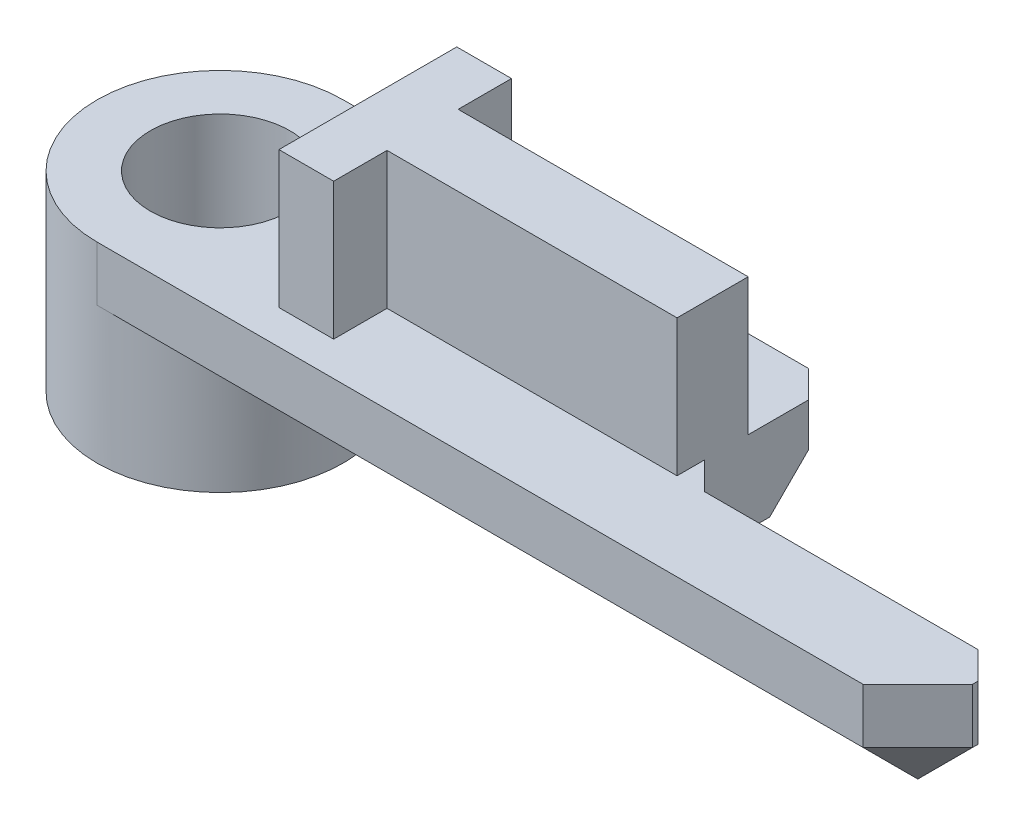
SolidWorks part; units mm, degrees
note: The reader was unsure of these and kept them because the rebuilt part matched: shared geometry of "Sketch3<4>".
ref_plane "Front Plane" through (0, 0, 0) normal (0, 0, 1) x (1, 0, 0)
ref_plane "Top Plane" through (0, 0, 0) normal (0, 1, 0) x (1, 0, 0)
ref_plane "Right Plane" through (0, 0, 0) normal (1, 0, 0) x (0, 0, -1)
sketch "Sketch1" plane through (0, 0, 0) normal (0, 1, 0) x (1, 0, 0)
  circle A0 centre (0, 0) radius 2.55
  circle A1 centre (0, 0) radius 4.5
  dimension "D1" = 5.1
  dimension "D2" = 9
extrude "Boss-Extrude1" add sketch "Sketch1" along normal blind 3
sketch "Sketch2" plane through (0, 3, 0) normal (0, 1, 0) x (1, 0, 0)
  line L1 (0, -4.5) -> (30, -4.5)
  line L3 (0, 4.5) -> (30, 4.5)
  line L4 (30, -4.5) -> (30, 4.5)
  circle A0 centre (0, 0) radius 2.55 construction
  circle A1 centre (0, 0) radius 4.5
  arc A2 (0, 4.5) -> (0, -4.5) centre (0, 0) ccw
  circle A3 centre (0, 0) radius 2.55
  dimension "D2" = 30
  dimension "D1" = 0
extrude "Boss-Extrude2" add sketch "Sketch2" along normal blind 4
chamfer "Chamfer1" distance 2 angle 45 5 edges at (15, 3, 4.5) (30, 5, 4.5) (30, 3, 0) (15, 3, -4.5) (30, 5, -4.5)
sketch "Sketch3" plane through (0, 7, 0) normal (0, 1, 0) x (1, 0, 0)
  line L0 (-4.5, 0) -> (6.4, 0) construction
  line L2 (5.4, -3.25) -> (7.4, -3.25)
  line L3 (5.4, -3.25) -> (5.4, 3.25)
  line L4 (5.4, 3.25) -> (7.4, 3.25)
  line L5 (0, -4.5) -> (28, -4.5)
  line L6 (28, -4.5) -> (30, -2.5)
  line L7 (30, -2.5) -> (30, 2.5)
  line L8 (30, 2.5) -> (28, 4.5)
  line L9 (28, 4.5) -> (0, 4.5)
  line L10 (0, -4.5) -> (28, -4.5)
  line L11 (28, -4.5) -> (30, -2.5)
  line L12 (30, -2.5) -> (30, 2.5)
  line L13 (30, 2.5) -> (28, 4.5)
  line L14 (28, 4.5) -> (0, 4.5)
  line L15 (7.4, -3.25) -> (7.4, -1.3)
  line L16 (5.4, -3.25) -> (7.4, 3.25) construction
  line L17 (5.4, 3.25) -> (7.4, -3.25) construction
  line L22 (18, -1.3) -> (18, 4.5)
  line L23 (7.4, -1.3) -> (18, -1.3)
  line L25 (7.4, 1.3) -> (7.4, 3.25)
  line L28 (30, -1.3) -> (18, -1.3)
  line L29 (7.4, 1.3) -> (18, 1.3)
  line L30 (18, 0) -> (30, 0) construction
  arc A1 (0, 4.5) -> (0, -4.5) centre (0, 0) ccw
  arc A2 (0, 4.5) -> (0, -4.5) centre (0, 0) ccw
  point P8 (6.4, 0)
  line M23 (30, 2.5) -> (28, 4.5)
  line M24 (28, 4.5) -> (0, 4.5)
  dimension "D2" = 2
  dimension "D3" = 12
  dimension "D4" = 5.8
  dimension "D5" = 6.5
  dimension "D7" = 6.4
  dimension "D1" = 0
extrude "Cut-Extrude1" cut sketch "Sketch3" against normal through all contours L28 L12 L22 M23 M24
extrude "Boss-Extrude4" add sketch "Sketch3<4>" along normal blind 5 contours L29 L25 L4 L3 L2 L15 L23 L22
sketch "Sketch3<4>" plane through (0, 7, 0) normal (0, 1, 0) x (1, 0, 0) same geometry as "Sketch3"
chamfer "Chamfer2" distance 1 angle 45 7 edges at (18, 6, -4.5) (18, 4, -3.5) (18, 3, -0.6) (30, 6, 1.3) (29, 4, 1.3) (23, 3, 1.3) (18, 5, 1.3)
